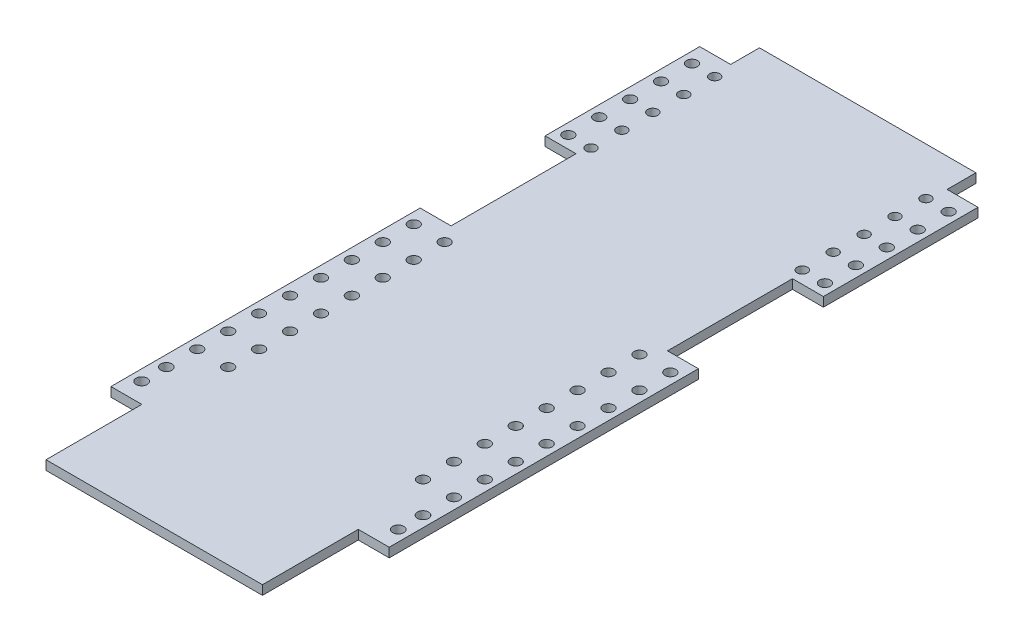
SolidWorks part; units mm, degrees
ref_plane "Front Plane" through (0, 0, 0) normal (0, 0, 1) x (1, 0, 0)
ref_plane "Top Plane" through (0, 0, 0) normal (0, 1, 0) x (1, 0, 0)
ref_plane "Right Plane" through (0, 0, 0) normal (1, 0, 0) x (0, 0, -1)
sketch "Sketch5" plane through (0, 0, 0) normal (0, 1, 0) x (1, 0, 0)
  line L0 (70, 36) -> (80, 36)
  line L1 (0, 0) -> (70, 0)
  line L2 (0, 0) -> (0, 235.74)
  line L3 (0, 235.74) -> (70, 235.74)
  line L4 (70, 0) -> (70, 235.74)
  line L5 (80, 36) -> (80, 136)
  line L6 (80, 136) -> (70, 136)
  line L7 (35, 235.74) -> (35, 0) construction
  line L8 (-10, 136) -> (0, 136)
  line L9 (-10, 36) -> (-10, 136)
  line L10 (0, 36) -> (-10, 36)
  dimension "D1" = 235.74
  dimension "D2" = 70
  dimension "D3" = 36
  dimension "D4" = 100
  dimension "D5" = 10
extrude "Boss-Extrude5" add sketch "Sketch5" along normal blind 3 contours L10 L2 L8 L9 | L7 L3 L2 L1 | L3 L7 L1 L4 | L5 L6 L4 L0 region at (75, 0, -86) region at (52.5, 0, -117.87) region at (17.5, 0, -117.87) region at (-5, 0, -86)
sketch "Sketch6" plane through (0, 3, 0) normal (0, 1, 0) x (1, 0, 0)
  point P0 (76.5, 50.4206)
  point P3 (76.5, 42.4206)
hole_wizard "M3 Clearance Hole1" positions "Sketch6" profile "Sketch7" hole size "M3" standard "ANSI Metric" end condition through all
sketch "Sketch7" plane through (76.5, 3, -50.4206) normal (1, 0, 0) x (0, 0, 1)
  line L0 (0, 0) -> (0, 3)
  line L1 (0, 3) -> (1.8, 3)
  line L2 (1.8, 3) -> (1.8, 0)
  line L5 (1.8, 0) -> (0, 0)
  line L11 (0, -6.35) -> (0, 107.95) construction
  dimension "Thru Hole Dia." = 3.6
  dimension "Thru Hole Depth" = 3
ref_plane "Plane1" through (35, 0, 0) normal (-1, 0, 0) x (0, 0, 1)
sketch "Sketch8" plane through (0, 3, 0) normal (0, 1, 0) x (1, 0, 0)
  line L0 (80, 36) -> (80, 136) construction
  circle A0 centre (76.5, 60.4206) radius 1.75
  circle A4 centre (76.5, 50.4206) radius 1.8 construction
  circle A6 centre (66.5, 60.4206) radius 1.75
  circle A7 centre (66.5, 70.4206) radius 1.75
  circle A8 centre (66.5, 80.4206) radius 1.75
  circle A9 centre (66.5, 90.4206) radius 1.75
  circle A10 centre (66.5, 100.4206) radius 1.75
  circle A11 centre (66.5, 110.4206) radius 1.75
  circle A12 centre (66.5, 120.4206) radius 1.75
  circle A13 centre (66.5, 130.4206) radius 1.75
  circle A14 centre (76.5, 70.4206) radius 1.75
  circle A15 centre (76.5, 80.4206) radius 1.75
  circle A16 centre (76.5, 90.4206) radius 1.75
  circle A17 centre (76.5, 100.4206) radius 1.75
  circle A18 centre (76.5, 110.4206) radius 1.75
  circle A19 centre (76.5, 120.4206) radius 1.75
  circle A20 centre (76.5, 130.4206) radius 1.75
  dimension "D1" = 3.5
  dimension "D3" = 10
  dimension "D2" = 3.5
  dimension "D4" = 2
  dimension "D5" = 8
extrude "Cut-Extrude1" cut sketch "Sketch8" against normal through all
sketch "Sketch10" plane through (0, 0, 0) normal (0, -1, 0) x (1, 0, 0)
  line L0 (70, -176.4206) -> (80, -176.4206)
  line L1 (70, -136) -> (70, -235.74) construction
  line L2 (80, -176.4206) -> (80, -226.4206)
  line L3 (80, -226.4206) -> (70, -226.4206)
  line L4 (70, -226.4206) -> (70, -176.4206)
  circle A0 centre (76.5, -180.4206) radius 1.75
  circle A4 centre (76.5, -130.4206) radius 1.75 construction
  circle A5 centre (76.5, -190.4206) radius 1.75
  circle A8 centre (76.5, -200.4206) radius 1.75
  circle A9 centre (76.5, -210.4206) radius 1.75
  circle A10 centre (76.5, -220.4206) radius 1.75
  dimension "D8" = 3.5
  dimension "D11" = 3.5
  dimension "D3" = 50
  dimension "D1" = 10
  dimension "D2" = 50
  dimension "D4" = 5
  dimension "D7" = 4
extrude "Boss-Extrude6" add sketch "Sketch10" against normal blind 3
sketch "Sketch11" plane through (0, 3, 0) normal (0, 1, 0) x (1, 0, 0)
  circle A13 centre (76.5, 180.4206) radius 1.75 construction
  circle A14 centre (76.5, 180.4206) radius 1.75 construction
  circle A15 centre (69.1652, 180.4206) radius 1.65
  circle A16 centre (69.1652, 190.4206) radius 1.65
  circle A17 centre (69.1652, 200.4206) radius 1.65
  circle A18 centre (69.1652, 210.4206) radius 1.65
  circle A19 centre (69.1652, 220.4206) radius 1.65
  dimension "D1" = 3.3
  dimension "D2" = 5
extrude "Cut-Extrude2" cut sketch "Sketch11" against normal through all
mirror "Mirror1" about plane through (35, 0, 0) normal (-1, 0, 0) of "Cut-Extrude2", "Boss-Extrude6", "M3 Clearance Hole1", "Cut-Extrude1"
sketch "Sketch12" plane through (0, 3, 0) normal (0, 1, 0) x (1, 0, 0)
  line L0 (70, 0) -> (70, 36) construction
  line L1 (0, 0) -> (70, 0)
  line L2 (0, 0) -> (0, 5)
  line L3 (0, 5) -> (70, 5)
  line L4 (70, 0) -> (70, 5)
  dimension "D1" = 5
extrude "Cut-Extrude3" cut sketch "Sketch12" against normal blind 10
equation "\"Spacing\"=8"
